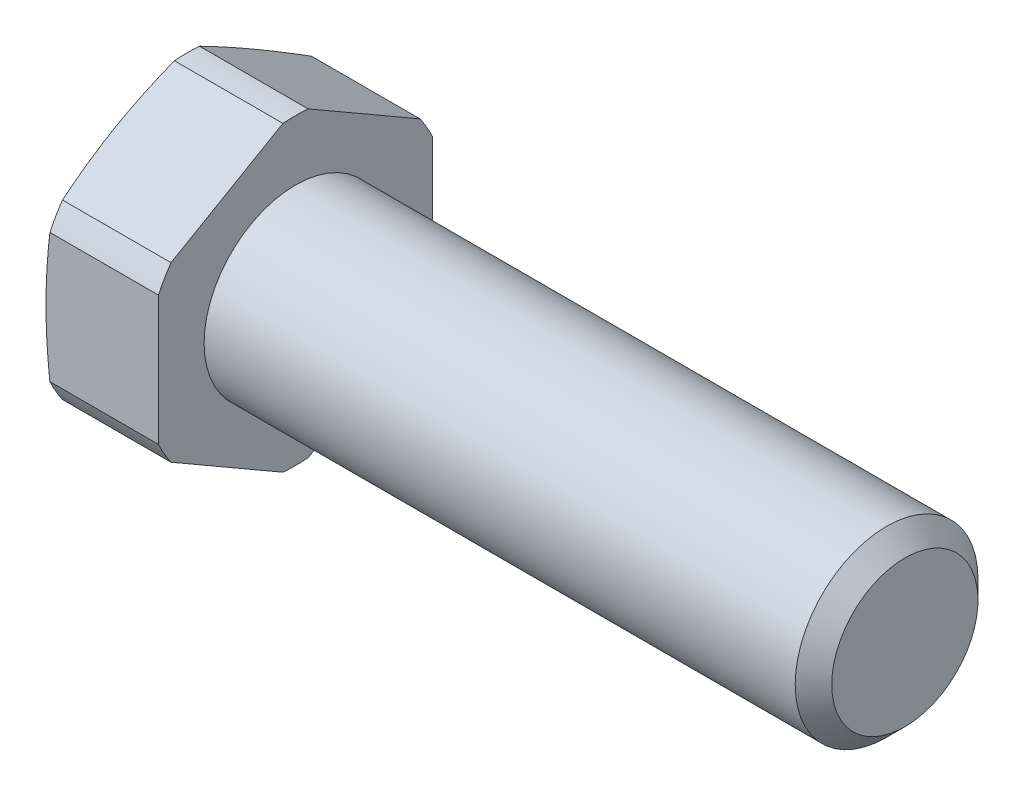
SolidWorks part; units mm, degrees
material "AISI 1020"
ref_plane "Спереди" through (0, 0, 0) normal (0, 0, 1) x (1, 0, 0)
ref_plane "Сверху" through (0, 0, 0) normal (0, 1, 0) x (1, 0, 0)
ref_plane "Справа" through (0, 0, 0) normal (1, 0, 0) x (0, 0, -1)
sketch "Эскиз1" plane through (0, 0, 0) normal (0, 0, 1) x (1, 0, 0)
  line L0 (-1000, 0) -> (49000, 0) construction
  line L1 (-7.5, 0) -> (-7.5, 8.55)
  line L2 (-7.5, 8.55) -> (-7.1249, 9.95)
  line L3 (-7.1249, 9.95) -> (0, 9.95)
  line L4 (0, 9.95) -> (0, 6)
  line L5 (0, 6) -> (38.8, 6)
  line L6 (40, 4.8) -> (40, 0)
  line L7 (40, 6) -> (40.875, 7.5155) construction
  line L8 (40.875, 7.5155) -> (41.75, 6) construction
  line L9 (41.75, 6) -> (40, 6) construction
  line L10 (40.875, 7.5155) -> (40.875, 6) construction
  line L11 (40.875, 7.5155) -> (10.875, 7.5155) construction
  line L12 (38.8, 6) -> (40, 4.8)
  line L13 (40, 6) -> (39.4, 5.4) construction
  line L14 (-7.5, 8.55) -> (-25.5, 8.55) construction
  line L15 (-7.5, 0) -> (40, 0)
  dimension "D1" = 1.2
  dimension "D2" = 15
revolve "Повернуть1" add sketch "Эскиз1" angle 360 about L0
cosmetic thread "Условное изображение резьбы1" parameters "D1"=30, "D2"=8.9689
sketch "Эскиз2" plane through (-7.5, 0, 0) normal (-1, 0, 0) x (0, 0, 1)
  line L1 (0, 10.3923) -> (-9, 5.1962)
  line L2 (-9, 5.1962) -> (-9, -5.1962)
  line L3 (-9, -5.1962) -> (0, -10.3923)
  line L4 (0, -10.3923) -> (9, -5.1962)
  line L5 (9, -5.1962) -> (9, 5.1962)
  line L6 (9, 5.1962) -> (0, 10.3923)
  circle A0 centre (0, 0) radius 9 construction
  dimension "D1" = 18
extrude "Вырез-Вытянуть1" cut sketch "Эскиз2" against normal up to surface (47.5 mm away) flip side to cut up to face at (40, 0, 4.8)
equation "\"D1@Эскиз1\"=\"_d_@Эскиз1\"/10"
equation "\"D@Эскиз1\"=\"S_@Эскиз1\"*0.95"
equation "\"D1@Эскиз2\"=\"S_@Эскиз1\""
equation "\"D1@Условное изображение резьбы1\"=\"b_@Эскиз1\""
equation "\"D2@Условное изображение резьбы1\"=\"_d_@Эскиз1\"-\"dr@Эскиз1\"*2"
